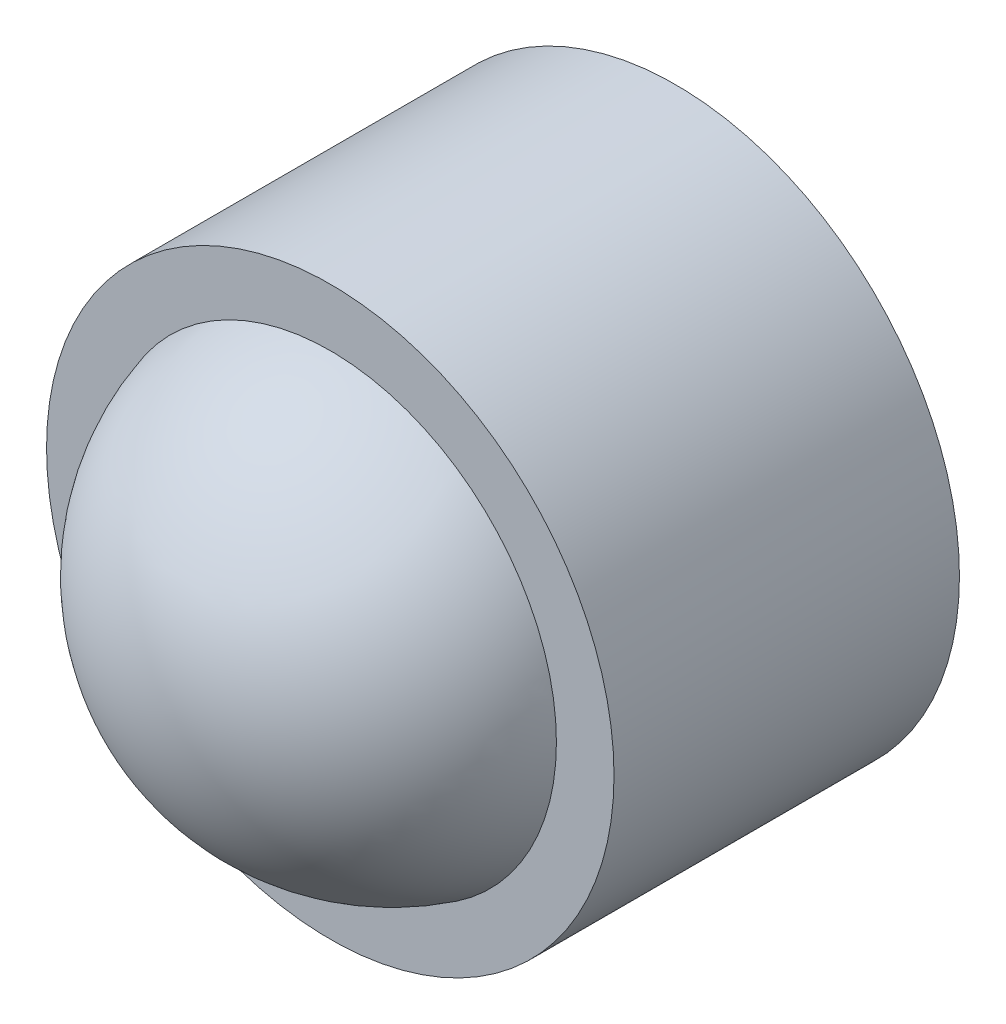
SolidWorks part; units mm, degrees
ref_plane "Ebene vorne" through (0, 0, 0) normal (0, 0, 1) x (1, 0, 0)
ref_plane "Ebene oben" through (0, 0, 0) normal (0, 1, 0) x (1, 0, 0)
ref_plane "Ebene rechts" through (0, 0, 0) normal (1, 0, 0) x (0, 0, -1)
sketch "Skizze1" plane through (0, 0, 0) normal (0, 0, 1) x (1, 0, 0)
  circle A0 centre (0, 0) radius 11.5
  circle A1 centre (-8, 0) radius 1
  circle A2 centre (8, 0) radius 1
  circle A3 centre (0, 0) radius 8
  dimension "D1" = 23
  dimension "D2" = 16
  dimension "D3" = 2
extrude "Body" add sketch "Skizze1" along normal blind 14 contours A0 A3 A2 A1 | A2 A3 A1 region at (-11.1747, 0, 0) region at (0, 0, 0)
sketch "Skizze2" plane through (0, 0, 0) normal (0, 1, 0) x (1, 0, 0)
  line L0 (0, 0) -> (0, -21.4988) construction
  line L2 (0, -21) -> (0, -2)
  circle A0 centre (0, -11.5) radius 9.5
  dimension "D1" = 21
  dimension "D2" = 19
revolve "Rotation1" add sketch "Skizze2" angle 360 about L0 region at (-4.0319, 0, 11.5)
